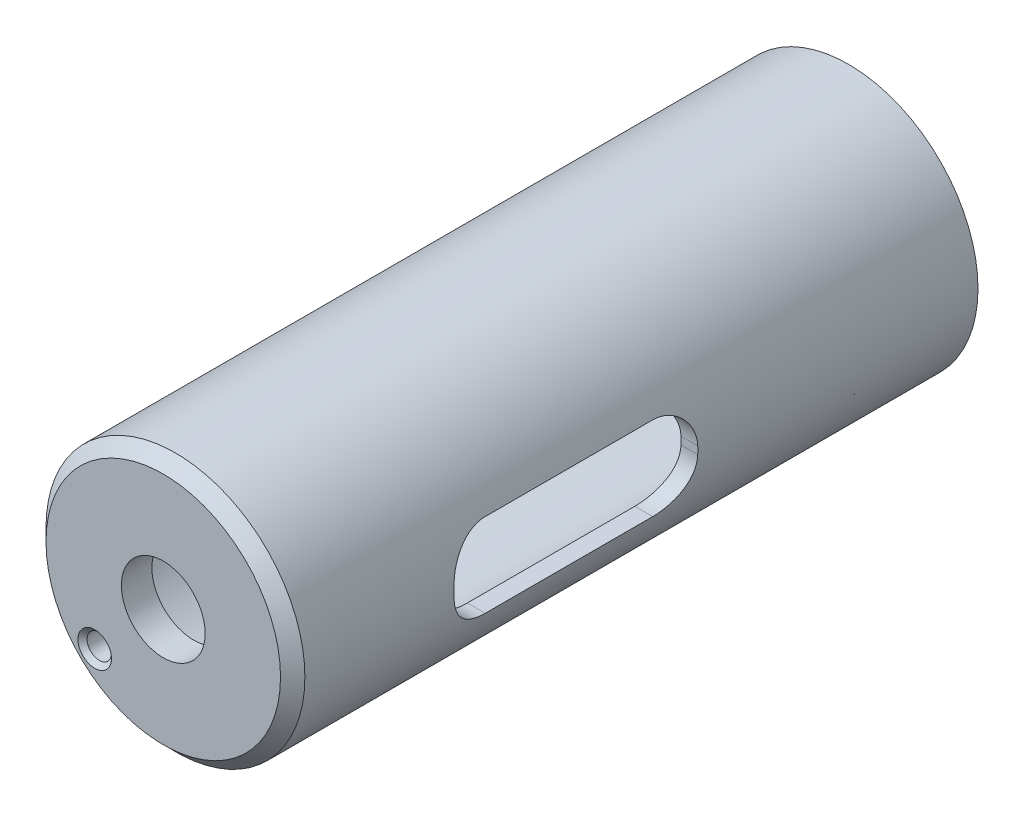
SolidWorks part; units mm, degrees
material "Простая углеродистая сталь"
ref_plane "Front" through (0, 0, 0) normal (0, 0, 1) x (1, 0, 0)
ref_plane "Top" through (0, 0, 0) normal (0, 1, 0) x (1, 0, 0)
ref_plane "Right" through (0, 0, 0) normal (1, 0, 0) x (0, 0, -1)
sketch "Эскиз1" plane through (0, 0, 0) normal (1, 0, 0) x (0, 0, -1)
  line L0 (0, 2.75) -> (0, 8.5)
  line L1 (0, 8.5) -> (45, 8.5)
  line L6 (45, 8.5) -> (45, 7.4)
  line L7 (45, 7.4) -> (2, 7.4)
  line L8 (2, 7.4) -> (2, 2.75)
  line L9 (2, 2.75) -> (0, 2.75)
  line L10 (0, 0) -> (54.2528, 0) construction
  dimension "D1" = 2.75
  dimension "D2" = 45
  dimension "D3" = 7.4
  dimension "D5" = 8.5
  dimension "D9" = 43
revolve "Повернуть1" add sketch "Эскиз1" angle 360 about L10
sketch "Эскиз2" plane through (0, 0, 0) normal (1, 0, 0) x (0, 0, -1)
  line L1 (13.1, -2.75) -> (24.1, -2.75)
  line L2 (10.6, -0.25) -> (10.6, 0.25)
  line L3 (13.1, 2.75) -> (24.1, 2.75)
  line L4 (26.6, -0.25) -> (26.6, 0.25)
  line L6 (45, -8.5) -> (45, 8.5) construction
  arc A0 (13.1, 2.75) -> (10.6, 0.25) centre (13.1, 0.25) ccw
  arc A1 (26.6, 0.25) -> (24.1, 2.75) centre (24.1, 0.25) ccw
  arc A2 (24.1, -2.75) -> (26.6, -0.25) centre (24.1, -0.25) ccw
  arc A3 (10.6, -0.25) -> (13.1, -2.75) centre (13.1, -0.25) ccw
  point P9 (10.6, 2.75)
  point P12 (26.6, 2.75)
  point P17 (10.6, -2.75)
  dimension "D5" = 2.5
  dimension "D1" = 5.5
  dimension "D2" = 16
  dimension "D3" = 2.75
  dimension "D4" = 18.4
extrude "Вырез-Вытянуть1" cut sketch "Эскиз2" along normal through all
chamfer "Фаска1" distance 0.8 angle 45 1 edges at (8.5, 0, 0)
sketch "Эскиз3" plane through (0, 0, 0) normal (-1, 0, 0) x (0, 0, -1)
  line L1 (2, 9.4774) -> (3.6, 9.4774)
  line L2 (2, 9.4774) -> (2, -10.0538)
  line L3 (2, -10.0538) -> (3.6, -10.0538)
  line L4 (3.6, 9.4774) -> (3.6, -10.0538)
  line L5 (45, -8.5) -> (45, 8.5) construction
  dimension "D1" = 1.6
  dimension "D2" = 43
extrude "Вырез-Вытянуть2" [suppressed] cut sketch "Эскиз3" along normal blind 0.7 from offset 8.5
hole_wizard "Отверстие обработанное метчиком M2x0.41" positions "Эскиз5" profile "Эскиз4" tap size "M2x0.4" standard "Ansi (метрические)" end condition up to next
sketch "Эскиз5" plane through (0, 0, 0) normal (0, 0, 1) x (1, 0, 0)
  circle A1 centre (0, 0) radius 2.75 construction
  point P0 (-4.5, -4.5)
  dimension "D2" = 4.5
  dimension "D1" = 4.5
sketch "Эскиз4" plane through (-4.5, -4.5, 0) normal (1, 0, 0) x (0, -1, 0)
  line L0 (0, 0) -> (0, 2)
  line L1 (0, 2) -> (1.05, 2)
  line L2 (0.8, 1.75) -> (0.8, 0.3)
  line L3 (0.8, 0.3) -> (1.1, 0)
  line L5 (1.1, 0) -> (0, 0)
  line L6 (-0.8, 0.3) -> (-1.1, 0) construction
  line L7 (1.05, 2) -> (0.8, 1.75)
  line L8 (-1.05, 2) -> (-0.8, 1.75) construction
  line L11 (0, -6.35) -> (0, 107.95) construction
  dimension "Диаметр проходного сверла" = 1.6
  dimension "Глубина проходного сверла" = 2
  dimension "Диаметр передней зенковки" = 2.2
  dimension "Угол передней зенковки" = 90
  dimension "Диаметр задней зенковки" = 2.1
  dimension "Угол задней зенковки" = 90
cosmetic thread "Отверстие резьбы3" parameters "D2"=2
